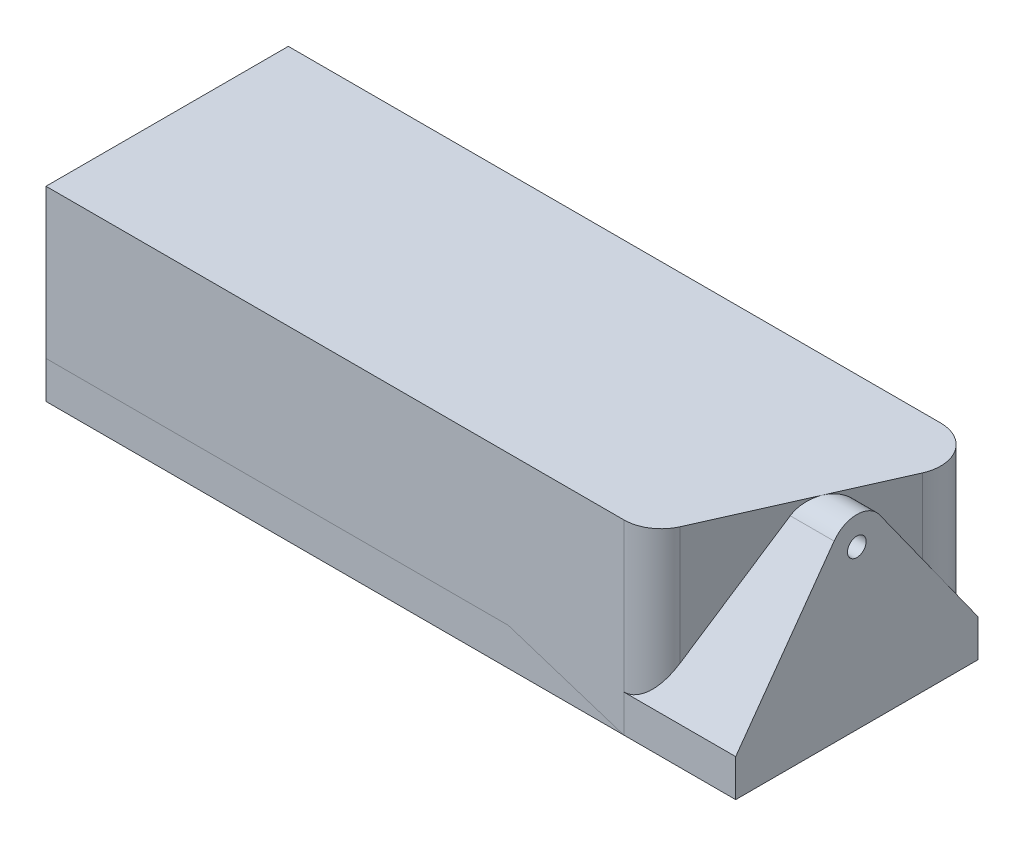
SolidWorks part; units mm, degrees
ref_plane "Front Plane" through (0, 0, 0) normal (0, 0, 1) x (1, 0, 0)
ref_plane "Top Plane" through (0, 0, 0) normal (0, 1, 0) x (1, 0, 0)
ref_plane "Right Plane" through (0, 0, 0) normal (1, 0, 0) x (0, 0, -1)
sketch "Sketch1" plane through (0, 0, 0) normal (0, 1, 0) x (1, 0, 0)
  line L0 (0, -10.3187) -> (0, 10.3187)
  line L1 (0, 10.3187) -> (55.5625, 10.3188)
  line L2 (58.4639, 5.8543) -> (52.1139, -8.4332)
  line L3 (49.2125, -10.3187) -> (0, -10.3187)
  arc A0 (55.5625, 10.3188) -> (58.4639, 5.8543) centre (55.5625, 7.1437) cw
  arc A1 (52.1139, -8.4332) -> (49.2125, -10.3187) centre (49.2125, -7.1437) cw
  point P3 (0, 0)
  point P4 (0, 0)
  point P11 (46.0375, 10.3187)
  point P12 (51.5536, -6.0549)
  point P13 (51.3212, -6.5632)
  dimension "D4" = 3.175
  dimension "D1" = 20.6375
  dimension "D2" = 46.0375
  dimension "D3" = 9.525
  dimension "D5" = 6.35
sketch "Sketch2" plane through (0, 0, 0) normal (0, 0, 1) x (1, 0, 0)
  line L0 (0, 0) -> (0, 3.175)
  line L1 (0, 3.175) -> (1.5875, 3.175)
  line L2 (1.5875, 3.175) -> (1.5875, 15.875)
  line L3 (1.5875, 15.875) -> (3.9688, 15.875)
  line L4 (3.9688, 15.875) -> (3.9688, 3.175)
  line L5 (3.9688, 3.175) -> (7.1438, 3.175)
  line L6 (7.1438, 3.175) -> (7.1438, 15.875)
  line L7 (7.1438, 15.875) -> (9.525, 15.875)
  line L8 (9.525, 15.875) -> (9.525, 3.175)
  line L9 (9.525, 3.175) -> (58.7375, 3.175)
  line L10 (58.7375, 3.175) -> (58.7375, 0)
  line L11 (58.7375, 0) -> (0, 0)
  dimension "D1" = 3.175
  dimension "D2" = 1.5875
  dimension "D3" = 12.7
  dimension "D4" = 2.3813
  dimension "D5" = 3.175
  dimension "D6" = 58.7375
sketch "Sketch3" plane through (0, 0, 0) normal (1, 0, 0) x (0, 0, -1)
  line L0 (10.3187, 0) -> (-10.3187, 0)
  line L2 (-10.3187, 0) -> (-10.3187, 3.175)
  line L3 (-10.3187, 3.175) -> (-1.936, 14.8802)
  line L4 (1.936, 14.8802) -> (10.3187, 3.175)
  line L5 (10.3187, 3.175) -> (10.3187, 0)
  arc A0 (-1.936, 14.8802) -> (1.936, 14.8802) centre (0, 13.4937) cw
  circle A1 centre (0, 13.4937) radius 0.7937
  point P3 (0, 0)
  point P4 (0, 0)
  point P11 (0, 0)
  point P12 (0, 0)
  point P13 (0, 0)
  dimension "D4" = 2.3813
  dimension "D1" = 20.6375
  dimension "D5" = 1.5875
  dimension "D2" = 3.175
  dimension "D3" = 10.3187
extrude "Boss-Extrude1" add sketch "Sketch1" along normal blind 15.875
extrude "Boss-Extrude2" add sketch "Sketch2" along normal blind 10.3187 and the other way blind 10.3187 separate body
extrude "Boss-Extrude3" add sketch "Sketch3" along normal blind 58.7375 separate body
equation "\"D6@Sketch2\"= \"D2@Sketch1\" + \"D3@Sketch1\" + \"D4@Sketch1\""
equation "\"D1@Sketch3\" = \"D1@Sketch1\""
equation "\"D2@Sketch3\"= \"D1@Sketch2\""
equation "\"D1@Boss-Extrude1\"= \"D1@Sketch2\" + \"D3@Sketch2\""
equation "\"D1@Boss-Extrude2\"= \"D1@Sketch1\" / 2"
equation "\"D2@Boss-Extrude2\" = \"D1@Boss-Extrude2\""
equation "\"D1@Boss-Extrude3\"= \"D2@Sketch1\" + \"D3@Sketch1\" + \"D4@Sketch1\""
